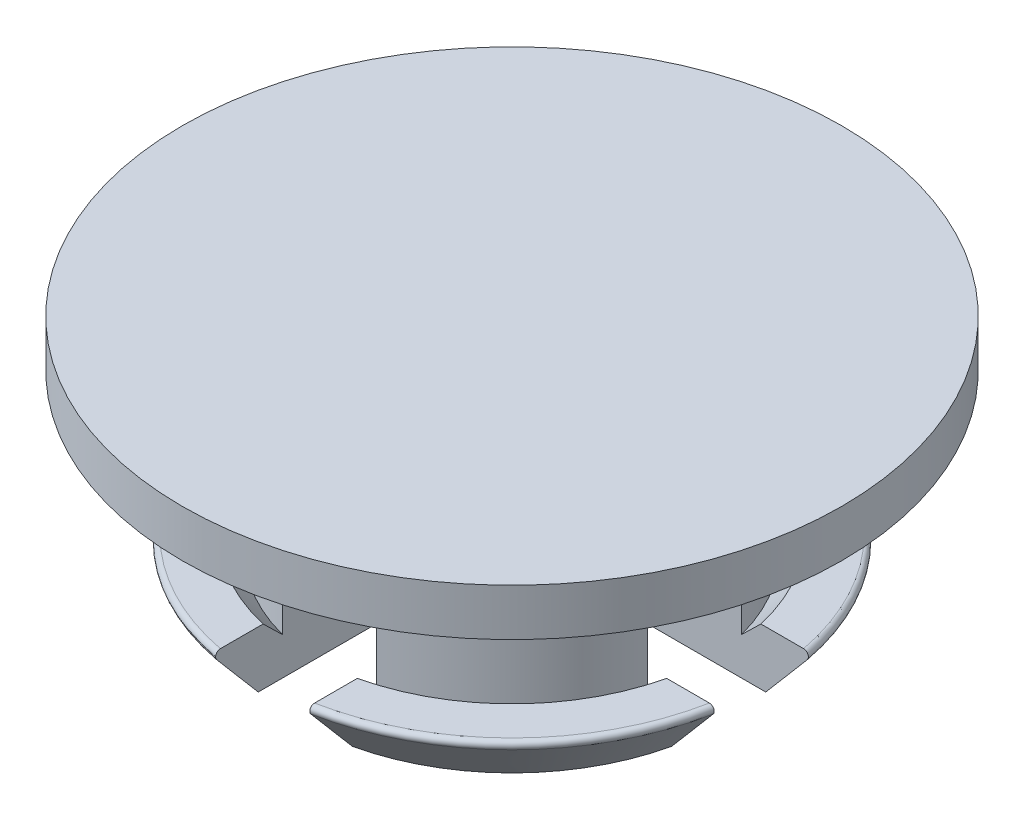
SolidWorks part; units mm, degrees
ref_plane "Front Plane" through (0, 0, 0) normal (0, 0, 1) x (1, 0, 0)
ref_plane "Top Plane" through (0, 0, 0) normal (0, 1, 0) x (1, 0, 0)
ref_plane "Right Plane" through (0, 0, 0) normal (1, 0, 0) x (0, 0, -1)
sketch "Szkic1" plane through (0, 0, 0) normal (0, 1, 0) x (1, 0, 0)
  circle A0 centre (0, 0) radius 7
  dimension "D1" = 14
extrude "Dodanie-wyciągnięcie1" add sketch "Szkic1" along normal blind 1
ref_point "Punkt1"
ref_plane "Płaszczyzna1" through (0, 0, 0) normal (0, -1, 0) x (-1, 0, 0)
sketch "Szkic2" plane through (0, 0, 0) normal (0, -1, 0) x (-1, 0, 0)
  circle A0 centre (0, 0) radius 4
  dimension "D1" = 8
extrude "Dodanie-wyciągnięcie2" add sketch "Szkic2" along normal blind 4.22
ref_axis "Oś1" through (0, -4.22, 0) along (0, 1, 0)
sketch "Szkic3" plane through (0, 0, 0) normal (1, 0, 0) x (0, 0, -1)
  line L0 (4, -4.22) -> (4.5, -4.22)
  line L1 (4.5, -4.22) -> (5.5, -3.02)
  line L2 (5.5, -3.02) -> (4.4, -3.02)
  line L3 (4.4, -3.02) -> (4, -3.42)
  line L4 (4, -3.42) -> (4, -4.22)
  line L5 (0, -4.22) -> (0, 0) construction
  line L6 (-7.7, 0) -> (7.7, 0) construction
  point P7 (0, 0)
  point P8 (0, 0)
  point P9 (4.3801, -2.7796)
  point P12 (5.5, -2.8)
  point P13 (4.436, -4)
  point P14 (4.3789, -2.8)
  dimension "D1" = 4
  dimension "D2" = 1.2
  dimension "D3" = 1.5
  dimension "D4" = 4.22
  dimension "D5" = 0.8
  dimension "D6" = 0.5
  dimension "D7" = 0.4
revolve "Obrót1" add sketch "Szkic3" angle 360 about axis through (0, -4.22, 0) along (0, 1, 0)
fillet "Zaokrąglenie1" radius 0.1 1 edges at (0, -3.02, -5.5)
ref_plane "Płaszczyzna2" through (0, -4.22, 0) normal (0, -1, 0) x (-1, 0, 0)
sketch "Szkic5" plane through (0, -4.22, 0) normal (0, -1, 0) x (-1, 0, 0)
  line L0 (-7.7941, -1) -> (-1, -1)
  line L1 (7.7941, 1) -> (1, 1)
  line L2 (-1, -7.7941) -> (-1, -1)
  line L3 (1, 7.7941) -> (1, 1)
  line L4 (-1, 1) -> (-1, 7.7941)
  line L5 (1, -1) -> (7.7941, -1)
  line L6 (1, -1) -> (1, -7.7941)
  line L7 (-1, 1) -> (-7.7941, 1)
  line L8 (-1, -1) -> (1, 1) construction
  arc A0 (-7.7941, 1) -> (-7.7941, -1) centre (0, 0) ccw
  arc A1 (-1, -7.7941) -> (1, -7.7941) centre (0, 0) ccw
  arc A2 (7.7941, -1) -> (7.7941, 1) centre (0, 0) ccw
  arc A3 (1, 7.7941) -> (-1, 7.7941) centre (0, 0) ccw
  point P1 (0, 0)
  point P15 (0, 0)
  dimension "D1" = 2
  dimension "D2" = 2
extrude "Wytnij-wyciągnięcie1" cut sketch "Szkic5" against normal blind 4.22
